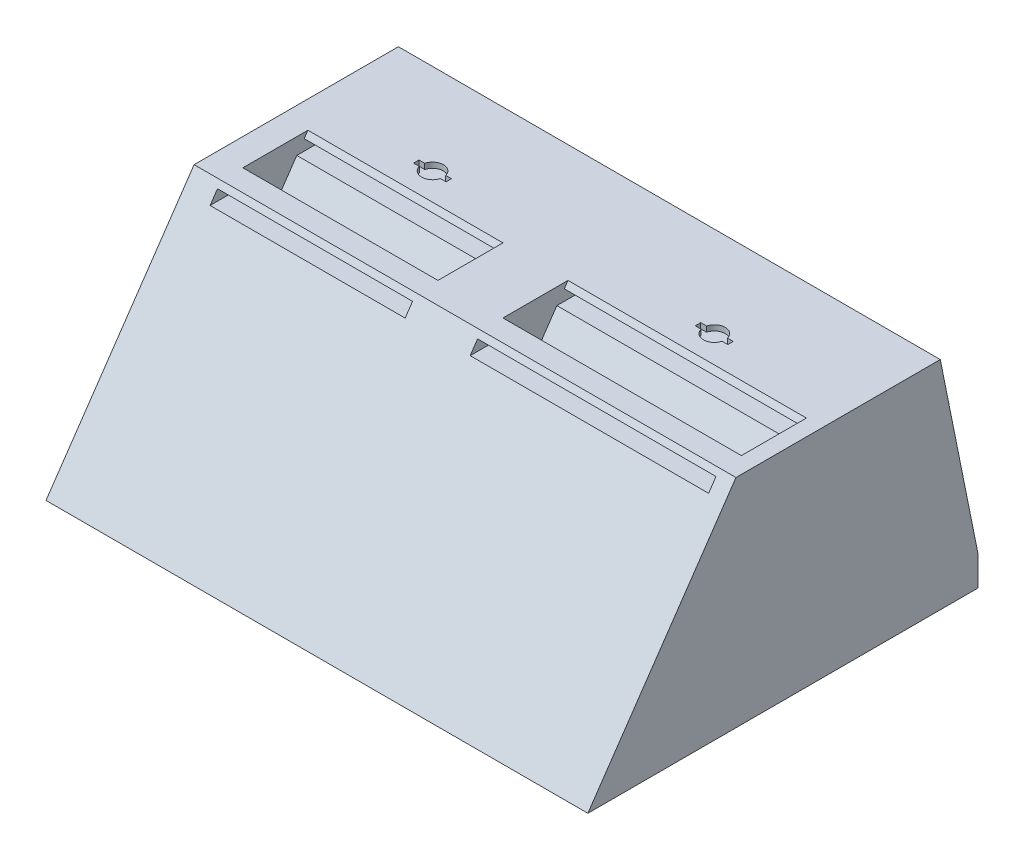
SolidWorks part; units mm, degrees
ref_plane "Ebene vorne" through (0, 0, 0) normal (0, 0, 1) x (1, 0, 0)
ref_plane "Ebene oben" through (0, 0, 0) normal (0, 1, 0) x (1, 0, 0)
ref_plane "Ebene rechts" through (0, 0, 0) normal (1, 0, 0) x (0, 0, -1)
sketch "Skizze1" plane through (0, 0, 0) normal (0, 0, 1) x (1, 0, 0)
  line L1 (-25, -15) -> (25, -15)
  line L2 (-25, -15) -> (-25, 15)
  line L3 (-25, 15) -> (25, 15)
  line L4 (25, -15) -> (25, 15)
  line L5 (-25, -15) -> (25, 15) construction
  line L6 (-25, 15) -> (25, -15) construction
  point P0 (0, 0)
  dimension "D1" = 50
  dimension "D2" = 30
extrude "Aufsatz-Linear austragen1" add sketch "Skizze1" along normal blind 40
ref_plane "Ebene1" through (0, 0, 0) normal (-1, 0, 0) x (0, 0, 1)
sketch "Skizze2" plane through (0, 0, 0) normal (-1, 0, 0) x (0, 0, 1)
  line L0 (7.5, 15) -> (28, -15)
  line L1 (40, 15) -> (0, 15) construction
  line L2 (40, -15) -> (0, -15) construction
  line L3 (28, -15) -> (34, -15)
  line L4 (34, -15) -> (13.5, 15)
  line L5 (13.5, 15) -> (7.5, 15)
  line L6 (40, 15) -> (40, -15) construction
  line L8 (26.6333, -13) -> (32.6333, -13)
  dimension "D1" = 6
  dimension "D2" = 6
  dimension "D3" = 7.5
  dimension "D4" = 2
extrude "FPV_Sender" cut sketch "Skizze2" against normal blind 22 from offset 1.5 contours L0 L8 L4 L5 region at (0, 1, 20.0667) offset against normal yes
sketch "Skizze4" plane through (0, 0, 0) normal (-1, 0, 0) x (0, 0, 1)
  line L0 (13.5, 15) -> (7.5, 15)
  line L1 (7.5, 15) -> (26.6333, -13)
  line L2 (7.5, 15) -> (26.6333, -13) construction
  line L3 (26.6333, -13) -> (32.6333, -13)
  line L4 (32.6333, -13) -> (13.5, 15) construction
  line L5 (32.6333, -13) -> (13.5, 15)
  dimension "D1" = 28
extrude "Empfänger" cut sketch "Skizze4" along normal blind 18 from offset 4.5
sketch "Skizze5" plane through (-25, 0, 0) normal (-1, 0, 0) x (0, 0, 1)
  line L0 (15.5, 15) -> (40, 15)
  line L1 (40, 15) -> (0, 15) construction
  line L2 (40, 15) -> (40, -20.8537)
  line L3 (40, 15) -> (40, -15) construction
  line L4 (40, -20.8537) -> (15.5, 15)
  line L5 (32.6333, -13) -> (13.5, 15) construction
  line L6 (5.5, 15) -> (0, -12.25)
  line L7 (0, 15) -> (0, -15) construction
  line L8 (0, -12.25) -> (0, 15)
  line L9 (0, 15) -> (5.5, 15)
  line L10 (40, -15) -> (0, -15) construction
  dimension "D1" = 2
  dimension "D2" = 2.75
  dimension "D3" = 2
extrude "Schnitt-Linear austragen3" cut sketch "Skizze5" against normal through all and the other way through all
sketch "Skizze7" plane through (25, 0, 0) normal (1, 0, 0) x (0, 0, -1)
  line L0 (-5.5, 15) -> (-15.5, 15)
  line L1 (-15.5, 15) -> (-22.3333, 5)
  line L2 (-15.5, 15) -> (-36, -15) construction
  line L3 (-22.3333, 5) -> (-3.4817, 5)
  line L4 (0, -12.25) -> (-5.5, 15) construction
  line L5 (-3.4817, 5) -> (-5.5, 15)
  dimension "D1" = 10
extrude "Schnitt-Linear austragen5" cut sketch "Skizze7" against normal up to surface (50 mm away) up to face at (-25, 0.55, 11.95)
shell "Wandung2" thickness 2 removed face at (0, -15, 18)
sketch "Skizze6" plane through (0, -13, 0) normal (0, 1, 0) x (1, 0, 0)
  line L0 (23.5, -26.6333) -> (1.5, -26.6333) construction
  line L1 (1.5, -32.6333) -> (8.5, -32.6333)
  line L2 (1.5, -32.6333) -> (1.5, -26.6333)
  line L3 (1.5, -26.6333) -> (8.5, -26.6333)
  line L4 (8.5, -32.6333) -> (8.5, -26.6333)
  dimension "D1" = 7
extrude "Schnitt-Linear austragen4" cut sketch "Skizze6" against normal up to surface (2 mm away) up to face at (0, -15, 18)
sketch "Skizze8" plane through (0, -13, 0) normal (0, 1, 0) x (1, 0, 0)
  line L0 (-22.5, -26.6333) -> (-4.5, -26.6333) construction
  line L1 (-4.5, -32.6333) -> (-8.5, -32.6333)
  line L2 (-4.5, -32.6333) -> (-4.5, -26.6333)
  line L3 (-4.5, -26.6333) -> (-8.5, -26.6333)
  line L4 (-8.5, -32.6333) -> (-8.5, -26.6333)
  dimension "D1" = 4
extrude "Schnitt-Linear austragen7" cut sketch "Skizze8" against normal up to surface (2 mm away) up to face at (5, -15, 29.6333)
sketch "Skizze9" plane through (-25, 0, 0) normal (-1, 0, 0) x (0, 0, 1)
  line L0 (22.675, 4.5) -> (7.675, 4.5)
  line L1 (22.3333, 5) -> (36, -15) construction
  line L2 (7.675, 4.5) -> (7.675, 3.5)
  line L3 (7.675, 3.5) -> (23.3583, 3.5)
  line L4 (23.3583, 3.5) -> (22.675, 4.5)
  line L5 (22.3333, 5) -> (3.4817, 5) construction
  dimension "D1" = 15
  dimension "D2" = 0.5
  dimension "D3" = 1
extrude "Schnitt-Linear austragen8" cut sketch "Skizze9" against normal blind 18 from offset 2.5 offset against normal yes
sketch "Skizze10" plane through (25, 0, 0) normal (1, 0, 0) x (0, 0, -1)
  line L0 (-22.675, 4.5) -> (-7.675, 4.5)
  line L2 (-22.675, 4.5) -> (-20.675, 4.5) construction
  line L3 (-7.675, 4.5) -> (-7.675, 3.5)
  line L4 (-7.675, 3.5) -> (-15.3583, 3.5) construction
  line L5 (-7.675, 3.5) -> (-23.3583, 3.5)
  line L6 (-23.3583, 3.5) -> (-22.675, 4.5)
  dimension "D1" = 15
extrude "Schnitt-Linear austragen9" cut sketch "Skizze10" against normal blind 22 from offset 1.5 offset against normal yes
sketch "Skizze12" plane through (-23, 0, 0) normal (1, 0, 0) x (0, 0, -1)
  line L0 (-5.1183, 3) -> (-13.2777, 3)
  line L1 (-13.2777, 3) -> (-15.3277, 0)
  line L3 (-25.5777, -15) -> (-13.2777, 3) construction
  line L4 (-15.3277, 0) -> (-4.5128, 0)
  line L5 (-5.1183, 3) -> (-2, -12.4498) construction
  line L6 (-4.5128, 0) -> (-5.1183, 3)
  dimension "D1" = 3
extrude "Aufsatz-Linear austragen2" add sketch "Skizze12" along normal up to surface (46 mm away) up to face at (23, -7.29, 9.5947)
sketch "Skizze11" plane through (0, 5, 0) normal (0, 1, 0) x (1, 0, 0)
  line L1 (14, -11.5833) -> (11, -11.5833)
  line L2 (14, -11.5833) -> (14, -12.0833)
  line L3 (14, -12.0833) -> (11, -12.0833)
  line L4 (11, -11.5833) -> (11, -12.0833)
  line L5 (14, -11.5833) -> (11, -12.0833) construction
  line L6 (14, -12.0833) -> (11, -11.5833) construction
  line L7 (23.5, -14.3333) -> (23.5, -20.3333) construction
  line L8 (23.5, -14.3333) -> (1.5, -14.3333) construction
  line L10 (-12, -12.0833) -> (-15, -12.0833)
  line L11 (-12, -12.0833) -> (-12, -11.5833)
  line L12 (-12, -11.5833) -> (-15, -11.5833)
  line L13 (-15, -12.0833) -> (-15, -11.5833)
  line L14 (-12, -12.0833) -> (-15, -11.5833) construction
  line L15 (-12, -11.5833) -> (-15, -12.0833) construction
  line L16 (-22.5, -14.3333) -> (-22.5, -20.3333) construction
  line L17 (-22.5, -14.3333) -> (-4.5, -14.3333) construction
  circle A0 centre (12.5, -11.8333) radius 1
  circle A1 centre (-13.5, -11.8333) radius 1
  dimension "D1" = 11
  dimension "D4" = 2
  dimension "D6" = 9
  dimension "D7" = 2
  dimension "D2" = 2.5
  dimension "D3" = 3
  dimension "D5" = 0.5
  dimension "D8" = 0.5
  dimension "D9" = 3
  dimension "D10" = 2.5
extrude "Schnitt-Linear austragen10" cut sketch "Skizze11" against normal up to surface (5 mm away) contours L10 A1 | A1 L12 L13 L10 | L10 A1 L12 | L12 A1 | A1 L10 L11 L12 | A0 L3 L2 L1 | L3 A0 | L1 A0 | L1 L4 L3 L2 region at (13.7447, 5, 11.8333) region at (12.5, 5, 11.271) region at (12.5, 5, 12.3957) region at (-12.2553, 5, 11.8333) region at (-13.5, 5, 12.3957) region at (-13.5, 5, 11.8333) region at (-14.7447, 5, 11.8333) region at (-13.5, 5, 11.271) up to face at (-0.5, 0, 11.7227)
